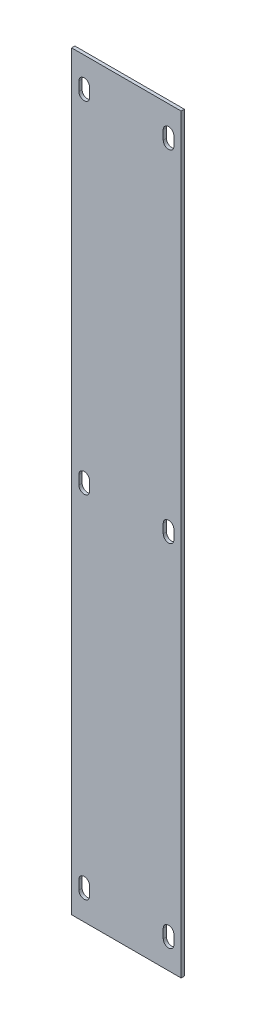
SolidWorks part; units mm, degrees
ref_plane "Front Plane" through (0, 0, 0) normal (0, 0, 1) x (1, 0, 0)
ref_plane "Top Plane" through (0, 0, 0) normal (0, 1, 0) x (1, 0, 0)
ref_plane "Right Plane" through (0, 0, 0) normal (1, 0, 0) x (0, 0, -1)
sketch "Sketch1" plane through (0, 0, 0) normal (0, 1, 0) x (1, 0, 0)
  line L1 (-13.85, -0.4064) -> (13.85, -0.4064)
  line L2 (-13.85, -0.4064) -> (-13.85, 0.4064)
  line L3 (-13.85, 0.4064) -> (13.85, 0.4064)
  line L4 (13.85, -0.4064) -> (13.85, 0.4064)
  line L5 (-13.85, -0.4064) -> (13.85, 0.4064) construction
  line L6 (-13.85, 0.4064) -> (13.85, -0.4064) construction
  point P0 (0, 0)
  dimension "D1" = 27.7
  dimension "D2" = 0.8128
extrude "Boss-Extrude1" add sketch "Sketch1" along normal blind 190.09
hole_wizard "M2.5 Clearance Slot2" positions "Sketch8" profile "Sketch9" size "M2.5" standard "ANSI Metric" slot yes end condition up to next
sketch "Sketch8" plane through (0, 0, -0.4064) normal (0, 0, -1) x (-1, 0, 0)
  line L1 (10.675, 0) -> (10.675, 190.09) construction
  line L3 (13.85, 190.09) -> (13.85, 0) construction
  line L4 (-10.675, 5) -> (-10.675, 10) construction
  line L5 (-13.85, 0) -> (13.85, 0) construction
  line L14 (-13.85, 0) -> (13.85, 0)
  line L15 (13.85, 0) -> (13.85, 190.09)
  line L16 (13.85, 190.09) -> (-13.85, 190.09)
  line L17 (-13.85, 190.09) -> (-13.85, 0)
  line L18 (-13.85, 0) -> (13.85, 0) construction
  line L19 (13.85, 0) -> (13.85, 190.09) construction
  line L20 (13.85, 190.09) -> (-13.85, 190.09) construction
  line L21 (-13.85, 190.09) -> (-13.85, 0) construction
  line L23 (-10.675, 182.59) -> (-10.675, 96.295) construction
  line L24 (-10.675, 96.295) -> (-10.675, 10) construction
  point P11 (-10.675, 7.5)
  point P23 (10.675, 7.5)
  point P28 (-10.675, 182.59)
  point P30 (10.675, 182.59)
  point P68 (-10.675, 96.295)
  point P76 (10.675, 96.295)
  point P86 (-10.675, 124.0811)
  point P87 (0, 0)
  point P88 (0, 0)
  point P89 (0, 0)
  point P90 (-10.675, 182.59)
  dimension "D1" = 3.175
  dimension "D2" = 3.175
  dimension "D3" = 5
  dimension "D4" = 7.5
  dimension "D5" = 7.5
  dimension "D6" = 0
sketch "Sketch9" plane through (-10.675, 96.295, -0.4064) normal (1, 0, 0) x (0, 1, 0)
  line L0 (0, 0) -> (0, 0.8128)
  line L1 (0, 0.8128) -> (1.35, 0.8128)
  line L2 (1.35, 0.8128) -> (1.35, 0)
  line L5 (1.35, 0) -> (0, 0)
  line L11 (0, -6.35) -> (0, 107.95) construction
  dimension "Thru Hole Dia." = 2.7
  dimension "Thru Hole Depth" = 0.8128
